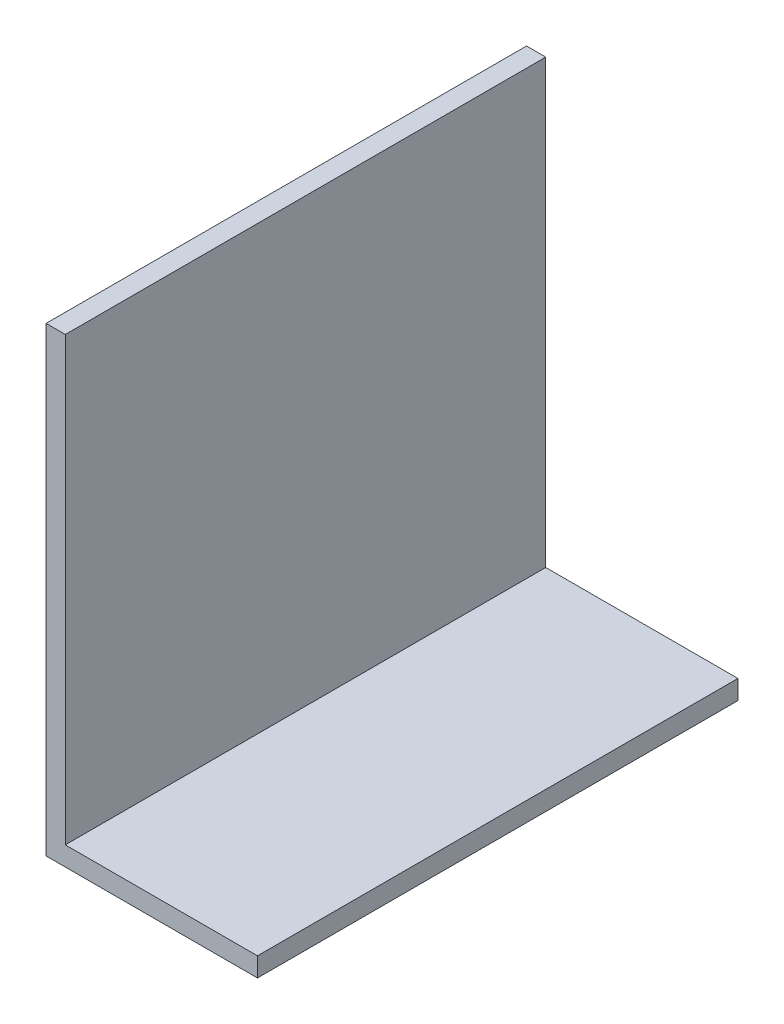
SolidWorks part; units mm, degrees
ref_plane "Front Plane" through (0, 0, 0) normal (0, 0, 1) x (1, 0, 0)
ref_plane "Top Plane" through (0, 0, 0) normal (0, 1, 0) x (1, 0, 0)
ref_plane "Right Plane" through (0, 0, 0) normal (1, 0, 0) x (0, 0, -1)
sketch "Sketch1" plane through (0, 0, 0) normal (0, 0, 1) x (1, 0, 0)
  line L0 (0, 72) -> (3, 72)
  line L1 (3, 3) -> (3, 72)
  line L9 (0, 72) -> (0, 0)
  line L10 (0, 0) -> (33, 0)
  line L11 (33, 0) -> (33, 3)
  line L12 (33, 3) -> (3, 3)
  dimension "D7" = 30
  dimension "D1" = 3
  dimension "D2" = 3
  dimension "D3" = 72
extrude "Boss-Extrude1" add sketch "Sketch1" along normal blind 75 contours L9 L10 L11 L12 L1 L0
equation "\"D2@Sketch1\"=\"D1@Sketch1\""
